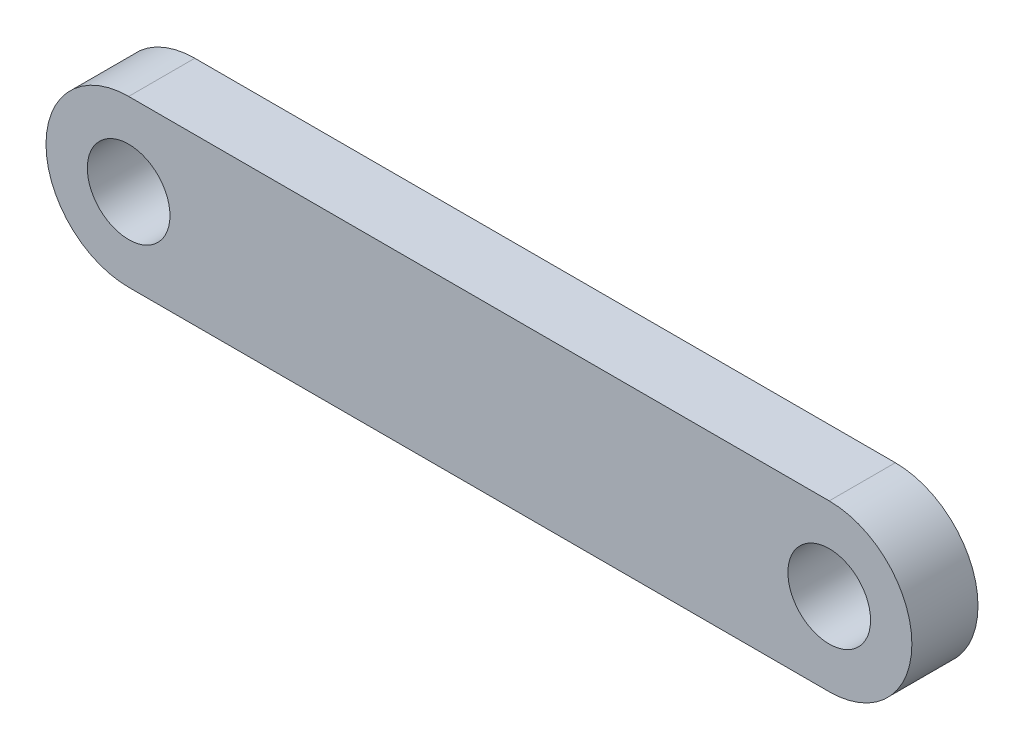
SolidWorks part; units mm, degrees
material "ABS"
ref_plane "Front Plane" through (0, 0, 0) normal (0, 0, 1) x (1, 0, 0)
ref_plane "Top Plane" through (0, 0, 0) normal (0, 1, 0) x (1, 0, 0)
ref_plane "Right Plane" through (0, 0, 0) normal (1, 0, 0) x (0, 0, -1)
sketch "Sketch1" plane through (0, 0, 0) normal (0, 0, 1) x (1, 0, 0)
  line L0 (0, 3.175) -> (26.9107, 3.175)
  line L1 (0, -3.175) -> (26.9107, -3.175)
  circle A0 centre (0, 0) radius 1.5875
  circle A1 centre (0, 0) radius 3.175
  circle A2 centre (26.9107, 0) radius 1.5875
  circle A3 centre (26.9107, 0) radius 3.175
  point P11 (25.9334, 0)
  point P12 (0, 0)
  point P13 (43.8368, 81.3925)
  point P14 (28.8072, 0)
  point P15 (26.7594, 0)
  point P16 (26.9107, 0)
  dimension "D1" = 3.175
  dimension "D2" = 6.35
extrude "Boss-Extrude2" add sketch "Sketch1" along normal blind 2.54 contours A1 A0 | A3 A2 | A3 L0 A1 L1 region at (13.4553, 0, 0) region at (2.1816, 2.1816, 0) region at (29.0922, 2.1816, 0)
